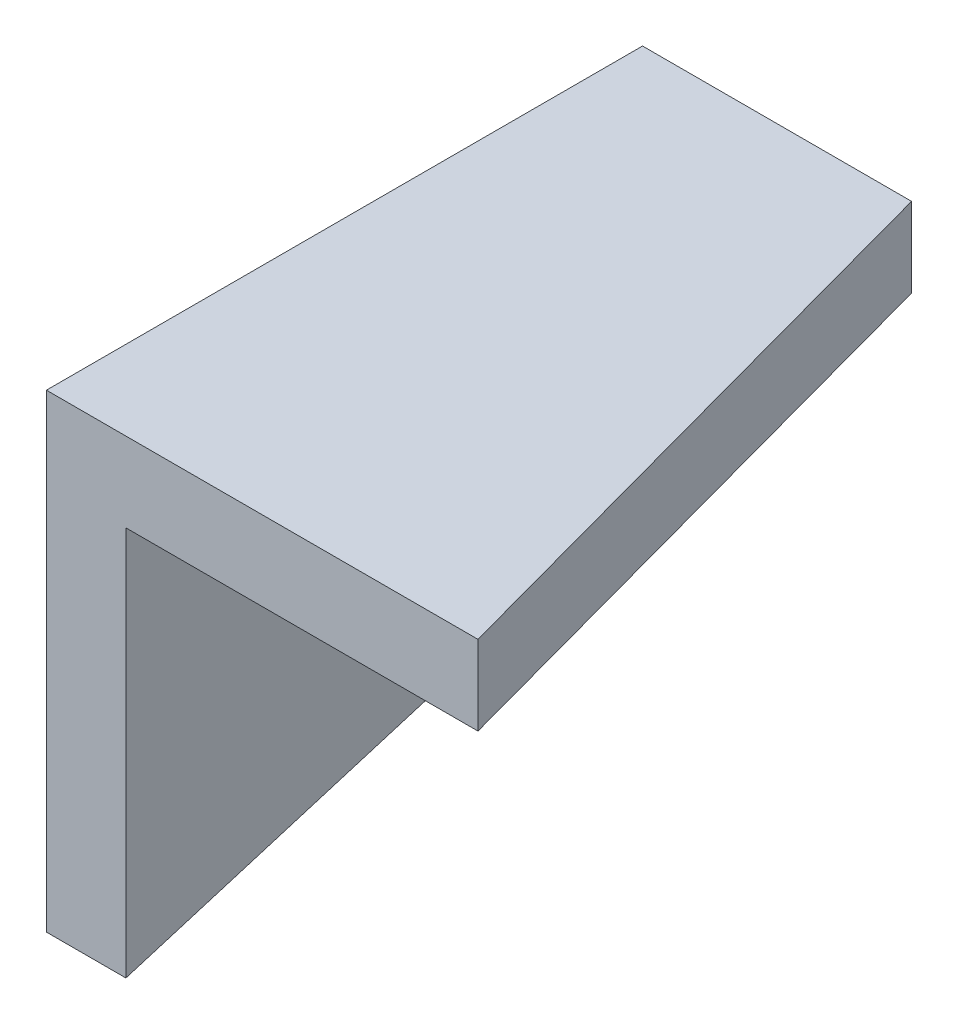
SolidWorks part; units mm, degrees
material "PLA"
ref_plane "Front Plane" through (0, 0, 0) normal (0, 0, 1) x (1, 0, 0)
ref_plane "Top Plane" through (0, 0, 0) normal (0, 1, 0) x (1, 0, 0)
ref_plane "Right Plane" through (0, 0, 0) normal (1, 0, 0) x (0, 0, -1)
sketch "Sketch1" plane through (0, 0, 0) normal (0, 0, 1) x (1, 0, 0)
  line L0 (40, 0) -> (0, 0)
  line L1 (0, 0) -> (0, -40)
  line L2 (40, 8) -> (-8, 8)
  line L3 (-8, 8) -> (-8, -40)
  line L4 (40, 0) -> (40, 8)
  line L5 (0, -40) -> (-8, -40)
  dimension "D1" = 40
  dimension "D2" = 40
  dimension "D3" = 8
extrude "Boss-Extrude1" add sketch "Sketch1" along normal mid plane 60
sketch "Sketch2" plane through (0, 0, 0) normal (0, -1, 0) x (1, 0, 0)
  line L0 (35.4354, 30) -> (19.0806, -30)
  line L1 (0, 30) -> (40, 30) construction
  line L2 (159.4514, 484.9707) -> (3.175, -88.3521) construction
  line L3 (0, -30) -> (40, -30) construction
  line L4 (19.0806, -30) -> (40, -30)
  line L5 (40, -30) -> (40, 30)
  line L6 (40, 30) -> (35.4354, 30)
extrude "Cut-Extrude1" cut sketch "Sketch2" against normal blind 10
sketch "Sketch3" plane through (0, 0, 0) normal (1, 0, 0) x (0, 0, -1)
  line L0 (30, 0) -> (30, -21.13) construction
  line L1 (30, -40) -> (30, 0) construction
  line L2 (30, -21.13) -> (-30, -39.24)
  line L3 (-30, -40) -> (-30, 0) construction
  line L4 (-30, -39.24) -> (-30, -40)
  line L5 (-30, -40) -> (30, -40)
  line L6 (30, -40) -> (30, -21.13)
  dimension "D1" = 21.13
  dimension "D2" = 39.24
extrude "Cut-Extrude2" cut sketch "Sketch3" against normal blind 10
